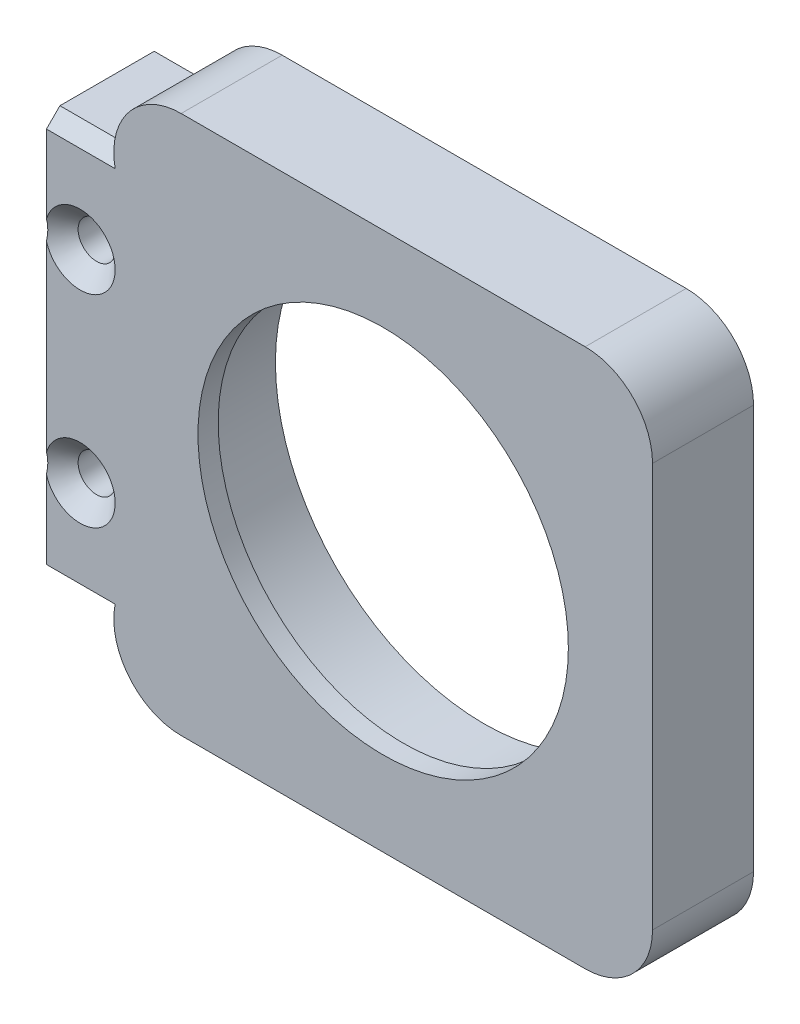
SolidWorks part; units mm, degrees
ref_plane "Front Plane" through (0, 0, 0) normal (0, 0, 1) x (1, 0, 0)
ref_plane "Top Plane" through (0, 0, 0) normal (0, 1, 0) x (1, 0, 0)
ref_plane "Right Plane" through (0, 0, 0) normal (1, 0, 0) x (0, 0, -1)
sketch "Sketch1" plane through (0, 0, 0) normal (0, 0, 1) x (1, 0, 0)
  line L1 (0, 0) -> (80, 0)
  line L2 (0, 0) -> (0, 80)
  line L3 (0, 80) -> (80, 80)
  line L4 (80, 0) -> (80, 80)
  dimension "D1" = 80
  dimension "D2" = 80
extrude "Boss-Extrude1" add sketch "Sketch1" along normal blind 15
sketch "Sketch2" plane through (0, 0, 15) normal (0, 0, 1) x (1, 0, 0)
  circle A0 centre (40, 40) radius 31
  dimension "D1" = 62
extrude "Cut-Extrude2" cut sketch "Sketch2" against normal through all
sketch "Sketch3" plane through (0, 0, 15) normal (0, 0, 1) x (1, 0, 0)
  circle A0 centre (40, 40) radius 31
  circle A1 centre (40, 40) radius 27.5
  dimension "D1" = 55
extrude "Boss-Extrude2" add sketch "Sketch3" against normal blind 3
fillet "Fillet1" radius 10 4 edges at (80, 80, 7.5) (80, 0, 7.5) (0, 0, 7.5) (0, 80, 7.5)
sketch "Sketch5" plane through (0, 0, 15) normal (0, 0, 1) x (1, 0, 0)
  line L1 (0, 70) -> (-10, 70)
  line L2 (0, 70) -> (0, 10)
  line L3 (0, 10) -> (-10, 10)
  line L4 (-10, 70) -> (-10, 10)
  dimension "D1" = 10
extrude "Boss-Extrude3" add sketch "Sketch5" against normal blind 20
sketch "Sketch6" plane through (0, 0, 15) normal (0, 0, 1) x (1, 0, 0)
  line L0 (-10, 40) -> (-5.4622, 40) construction
  line L1 (-10, 70) -> (-10, 10) construction
  line L3 (0, 70) -> (-10, 70) construction
  circle A0 centre (-5, 55) radius 2.5
  circle A2 centre (-5, 25) radius 2.5
  dimension "D2" = 15
  dimension "D4" = 5
extrude "Cut-Extrude3" cut sketch "Sketch6" against normal through all
chamfer "Chamfer1" distance 2 angle 45 2 edges at (-5, 10, 15) (-5, 70, 15)
hole_wizard "CSK for M5 Flat Head Machine Screw2" positions "Sketch9" profile "Sketch10" countersink size "M5" standard "ANSI Metric" end condition through all
sketch "Sketch9" plane through (0, 0, 15) normal (0, 0, 1) x (1, 0, 0)
  point P0 (-5, 55)
  point P3 (-5, 25)
sketch "Sketch10" plane through (-5, 55, 15) normal (1, 0, 0) x (0, -1, 0)
  line L0 (0, 0) -> (0, 20)
  line L1 (0, 20) -> (2.75, 20)
  line L2 (2.75, 20) -> (2.75, 2.45)
  line L3 (2.75, 2.45) -> (5.2, 0)
  line L5 (5.2, 0) -> (0, 0)
  line L6 (-2.75, 2.45) -> (-5.2, 0) construction
  line L11 (0, -6.35) -> (0, 107.95) construction
  dimension "Thru Hole Dia." = 5.5
  dimension "Thru Hole Depth" = 20
  dimension "Near C'Sink Dia." = 10.4
  dimension "Near C'Sink Angle" = 90
chamfer "Chamfer2" distance 4 angle 45 2 edges at (-5, 10, -5) (-5, 70, -5)
sketch "Sketch11" plane through (-10, 0, 0) normal (-1, 0, 0) x (0, 0, 1)
  line L0 (15, 40) -> (-15, 40) construction
  line L1 (15, 53.5717) -> (15, 26.4283) construction
  circle A0 centre (-15, 40) radius 15
  dimension "D2" = 30
  dimension "D1" = 30
extrude "Cut-Extrude4" cut sketch "Sketch11" against normal blind 2
